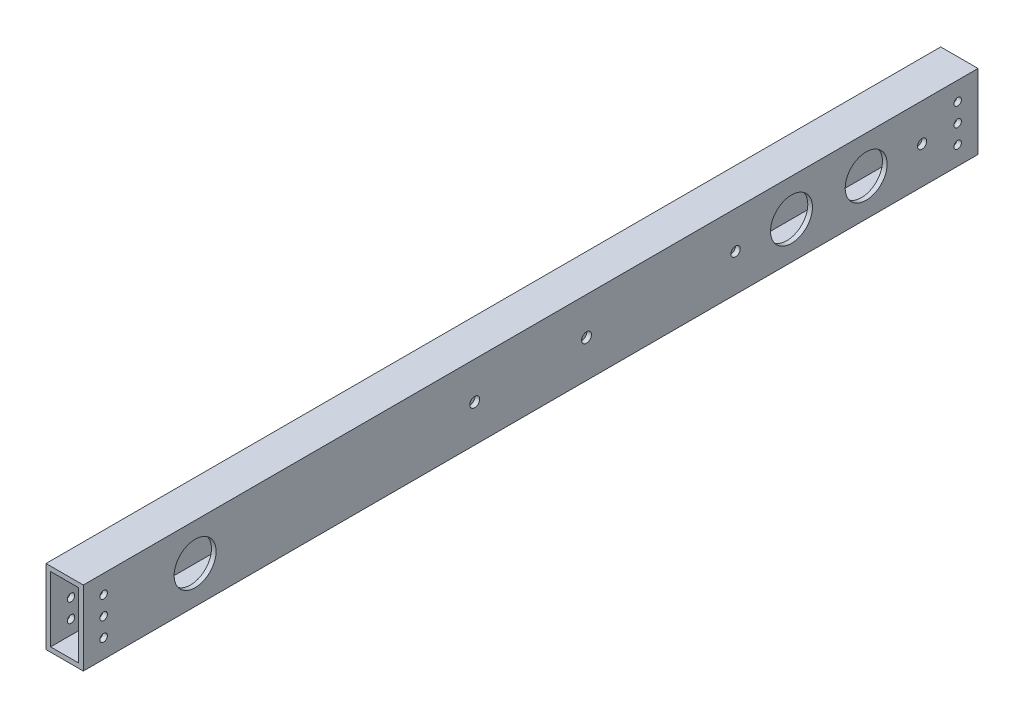
SolidWorks part; units mm, degrees
ref_plane "Front Plane" through (0, 0, 0) normal (0, 0, 1) x (1, 0, 0)
ref_plane "Top Plane" through (0, 0, 0) normal (0, 1, 0) x (1, 0, 0)
ref_plane "Right Plane" through (0, 0, 0) normal (1, 0, 0) x (0, 0, -1)
sketch "Sketch1" plane through (0, 0, 0) normal (0, 0, 1) x (1, 0, 0)
  line L0 (-9.525, 22.225) -> (9.525, 22.225)
  line L1 (-12.7, 25.4) -> (12.7, 25.4)
  line L2 (-12.7, 25.4) -> (-12.7, -25.4)
  line L3 (-12.7, -25.4) -> (12.7, -25.4)
  line L4 (12.7, 25.4) -> (12.7, -25.4)
  line L5 (-12.7, 25.4) -> (12.7, -25.4) construction
  line L6 (-12.7, -25.4) -> (12.7, 25.4) construction
  line L7 (9.525, 22.225) -> (9.525, -22.225)
  line L8 (-9.525, -22.225) -> (9.525, -22.225)
  line L9 (-9.525, 22.225) -> (-9.525, -22.225)
  point P0 (0, 0)
  dimension "D1" = 50.8
  dimension "D2" = 25.4
  dimension "D3" = 3.175
extrude "Boss-Extrude1" add sketch "Sketch1" along normal mid plane 609.6
hole_wizard "#10 Clearance Hole1" positions "Sketch4" profile "Sketch3" hole size "#10" standard "ANSI Inch" end condition through all
sketch "Sketch4" plane through (12.7, 0, 0) normal (1, 0, 0) x (0, 0, -1)
  line L0 (-304.8, 25.4) -> (304.8, 25.4) construction
  point P0 (-290.9409, 12.7)
  point P13 (-290.9409, 0)
  point P14 (-290.9409, -12.7)
  dimension "D2" = 12.7
  dimension "D1" = 3
sketch "Sketch3" plane through (12.7, 12.7, 290.9409) normal (0, 1, 0) x (0, 0, -1)
  line L0 (0, 0) -> (0, 25.4)
  line L1 (0, 25.4) -> (2.5527, 25.4)
  line L2 (2.5527, 25.4) -> (2.5527, 0)
  line L5 (2.5527, 0) -> (0, 0)
  line L11 (0, -6.35) -> (0, 107.95) construction
  dimension "Thru Hole Dia." = 5.1054
  dimension "Thru Hole Depth" = 25.4
mirror "Mirror1" about plane through (0, 0, 0) normal (0, 0, 1) of "#10 Clearance Hole1"
hole_wizard "1/4 Clearance Hole2" positions "Sketch6" profile "Sketch5" hole size "1/4" standard "ANSI Inch" end condition through all
sketch "Sketch6" plane through (12.7, 0, 0) normal (1, 0, 0) x (0, 0, -1)
  line L0 (-38.1, 0) -> (38.1, 0) construction
  point P0 (-38.1, 0)
  point P2 (38.1, 0)
  dimension "D1" = 76.2
sketch "Sketch5" plane through (12.7, 0, 38.1) normal (0, 1, 0) x (0, 0, -1)
  line L0 (0, 0) -> (0, 25.4)
  line L1 (0, 25.4) -> (3.3782, 25.4)
  line L2 (3.3782, 25.4) -> (3.3782, 0)
  line L5 (3.3782, 0) -> (0, 0)
  line L11 (0, -6.35) -> (0, 107.95) construction
  dimension "Thru Hole Dia." = 6.7564
  dimension "Thru Hole Depth" = 25.4
sketch "Sketch7" plane through (12.7, 0, 0) normal (1, 0, 0) x (0, 0, -1)
  line L0 (304.8, -25.4) -> (304.8, 25.4) construction
  line L1 (-304.8, -25.4) -> (-304.8, 25.4) construction
  line L2 (139.6238, 0) -> (266.7, 0) construction
  line L3 (279.4, -25.4) -> (279.4, 25.4) construction
  line L4 (-304.8, -25.4) -> (304.8, -25.4) construction
  line L5 (-304.8, 25.4) -> (304.8, 25.4) construction
  circle A0 centre (-228.6, 0) radius 14.2875
  circle A1 centre (177.7238, 0) radius 14.2875
  circle A2 centre (228.6, 0) radius 14.2875
  circle A3 centre (177.7238, 0) radius 26.67 construction
  circle A4 centre (228.6, 0) radius 26.67 construction
  circle A5 centre (139.6238, 0) radius 3.175
  circle A6 centre (266.7, 0) radius 3.175
  circle A7 centre (139.6238, 0) radius 6.35 construction
  dimension "D1" = 28.575
  dimension "D2" = 28.575
  dimension "D7" = 53.34
  dimension "D8" = 6.35
  dimension "D12" = 12.7
  dimension "D3" = 50.8762
  dimension "D4" = 76.2
  dimension "D5" = 76.2
  dimension "D6" = 406.3238
  dimension "D9" = 38.1
  dimension "D10" = 38.1
  dimension "D11" = 127.0762
  dimension "D13" = 25.4
extrude "Cut-Extrude1" cut sketch "Sketch7" against normal through all
